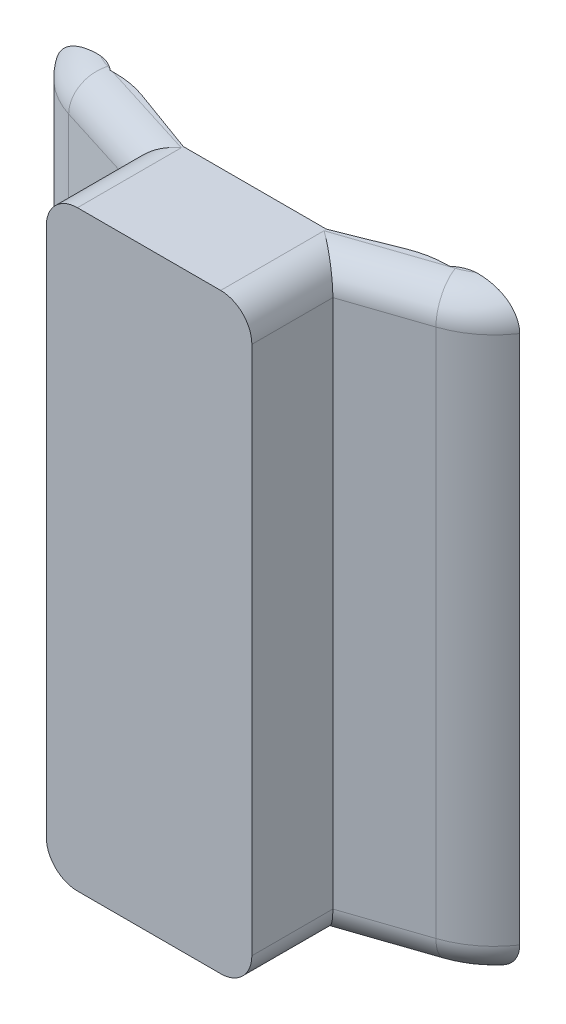
SolidWorks part; units mm, degrees
ref_plane "Front Plane" through (0, 0, 0) normal (0, 0, 1) x (1, 0, 0)
ref_plane "Top Plane" through (0, 0, 0) normal (0, 1, 0) x (1, 0, 0)
ref_plane "Right Plane" through (0, 0, 0) normal (1, 0, 0) x (0, 0, -1)
sketch "Sketch2" plane through (0, 0, 0) normal (0, 1, 0) x (1, 0, 0)
  line L0 (-16.5, 6.5) -> (-37.9889, 13.2596)
  line L1 (16.5, 6.5) -> (36.5, 13.2596)
  line L2 (-16.5, 6.5) -> (-16.5, -6.5)
  line L3 (-16.5, -6.5) -> (16.5, -6.5)
  line L4 (16.5, 6.5) -> (16.5, -6.5)
  line L5 (26.5, 16.5) -> (26.5, 15.2238)
  line L6 (26.5, 15.2238) -> (23.2995, 15.2238)
  line L7 (26.5, 16.5) -> (36.5, 16.5)
  line L8 (-27.9705, 15.2238) -> (-27.9705, 16.4405)
  line L9 (-24.4816, 15.2238) -> (-27.9705, 15.2238)
  line L10 (-27.9705, 16.4405) -> (-27.9705, 16.5)
  line L11 (-27.9889, 16.5) -> (-27.9705, 16.5)
  line L12 (-27.9705, 16.5) -> (-27.9703, 16.4997)
  line L13 (-27.9889, 16.5) -> (-37.9889, 16.5)
  line L14 (26.5, 16.5) -> (36.5, 16.5)
  line L17 (-37.9889, 16.5) -> (-27.9889, 16.5)
  line L18 (36.5, 16.5) -> (36.5, 13.2596)
  line L21 (-37.9889, 13.2596) -> (-37.9889, 16.5)
  line L22 (-37.9889, 16.5) -> (-27.9889, 16.5)
  line L23 (36.5, 16.5) -> (26.5, 16.5)
  line L24 (-11.5, 10.5) -> (11.4535, 10.5) construction
  line L27 (-11.5, 10.5) -> (11.4535, 10.5)
  line L28 (11.4535, 10.5) -> (23.2995, 15.2238)
  line L29 (-11.5, 10.5) -> (-24.4816, 15.2238)
  point P0 (0, 0)
  dimension "D1" = 13
  dimension "D2" = 33
  dimension "D5" = 10
  dimension "D6" = 10
extrude "Boss-Extrude5" add sketch "Sketch2" along normal blind 95 contours L27 L29 L9 L8 L10 L11 L13 L21 L0 L2 L3 L4 L1 L18 L7 L5 L6 L28 region at (-0.2815, 0, -5.07)
fillet "Fillet16" radius 15 1 edges at (36.5, 47.5, -13.2596)
fillet "Fillet17" radius 15 1 edges at (-37.9889, 47.5, -13.2596)
fillet "Fillet18" radius 15 1 edges at (23.2995, 47.5, -15.2238)
fillet "Fillet19" radius 15 1 edges at (-24.4816, 47.5, -15.2238)
fillet "Fillet21" radius 5 1 edges at (26.5, 47.5, -16.5)
fillet "Fillet22" radius 5 1 edges at (-27.9705, 47.5, -16.5)
fillet "Fillet23" radius 5 2 edges at (-23.3583, 0, -8.6574) (-34.5714, 0, -13.0167)
fillet "Fillet24" radius 5 2 edges at (22.6846, 0, -8.5903) (33.1626, 0, -12.9636)
fillet "Fillet25" radius 5 2 edges at (33.1626, 95, -12.9636) (22.6846, 95, -8.5903)
fillet "Fillet26" radius 5 2 edges at (-34.5714, 95, -13.0167) (-23.3583, 95, -8.6574)
fillet "Fillet28" radius 5 1 edges at (16.5, 0, -2.6389)
fillet "Fillet29" radius 5 1 edges at (-16.5, 0, -2.6208)
fillet "Fillet30" radius 5 1 edges at (-16.5, 95, -2.6208)
fillet "Fillet31" radius 5 1 edges at (16.5, 95, -2.6389)
